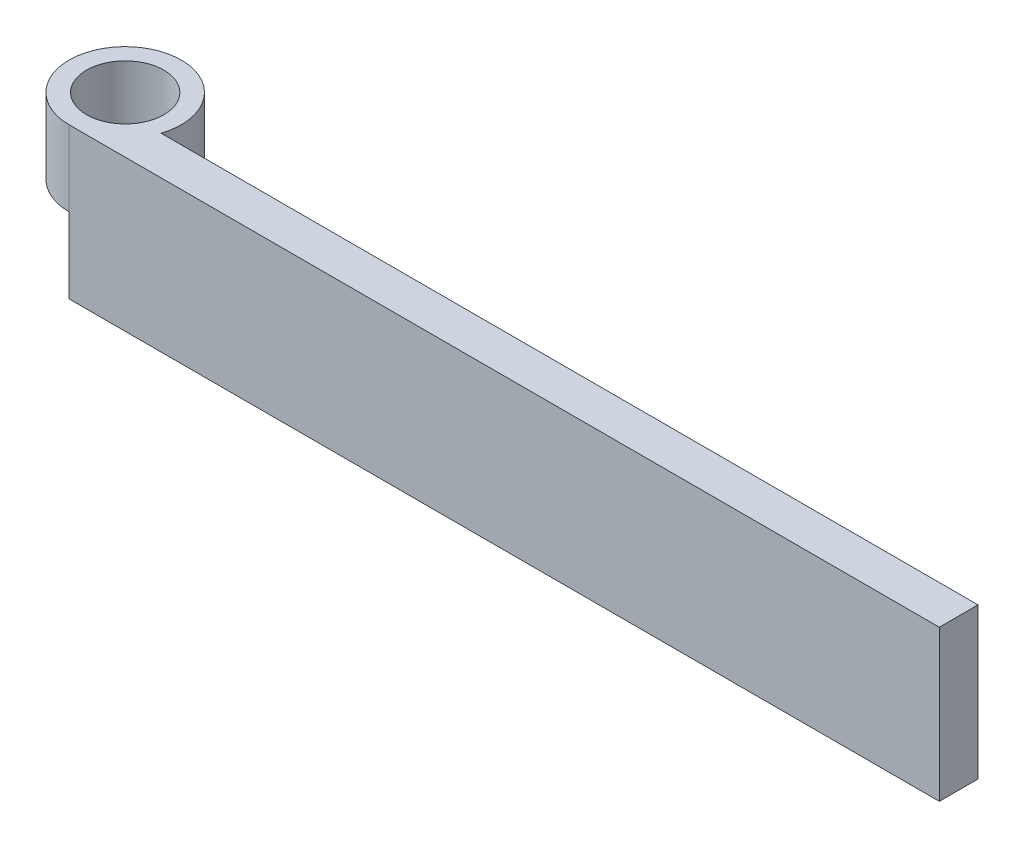
SolidWorks part; units mm, degrees
ref_plane "Alzado" through (0, 0, 0) normal (0, 0, 1) x (1, 0, 0)
ref_plane "Planta" through (0, 0, 0) normal (0, 1, 0) x (1, 0, 0)
ref_plane "Vista lateral" through (0, 0, 0) normal (1, 0, 0) x (0, 0, -1)
sketch "Croquis1" plane through (0, 0, 0) normal (0, 1, 0) x (1, 0, 0)
  line L0 (-14.1349, 0) -> (21.0104, 0) construction
  line L1 (0, 9.8879) -> (0, -9.2182) construction
  circle A0 centre (0, 0) radius 2.9
  circle A1 centre (0, 0) radius 2
  dimension "D1" = 5.8
  dimension "D2" = 4
extrude "Saliente-Extruir1" add sketch "Croquis1" along normal blind 3.9
sketch "Croquis3" plane through (0, 0, 0) normal (0, -1, 0) x (1, 0, 0)
  line L0 (0, 4.5432) -> (0, 2.9) construction
  line L1 (0, 2.9) -> (45, 2.9)
  line L2 (45, 2.9) -> (45, 0.9)
  line L3 (45, 0.9) -> (2.7568, 0.9)
  line L5 (0, 5.0665) -> (0, -5.1763) construction
  circle A0 centre (0, 0) radius 2.9
  dimension "D1" = 5.8
  dimension "D2" = 45
  dimension "D3" = 2
extrude "Saliente-Extruir2" add sketch "Croquis3" along normal blind 3.9 and the other way blind 3.9 contours L3 L2 L1 L5 region at (23.5049, 0, 1.908)
